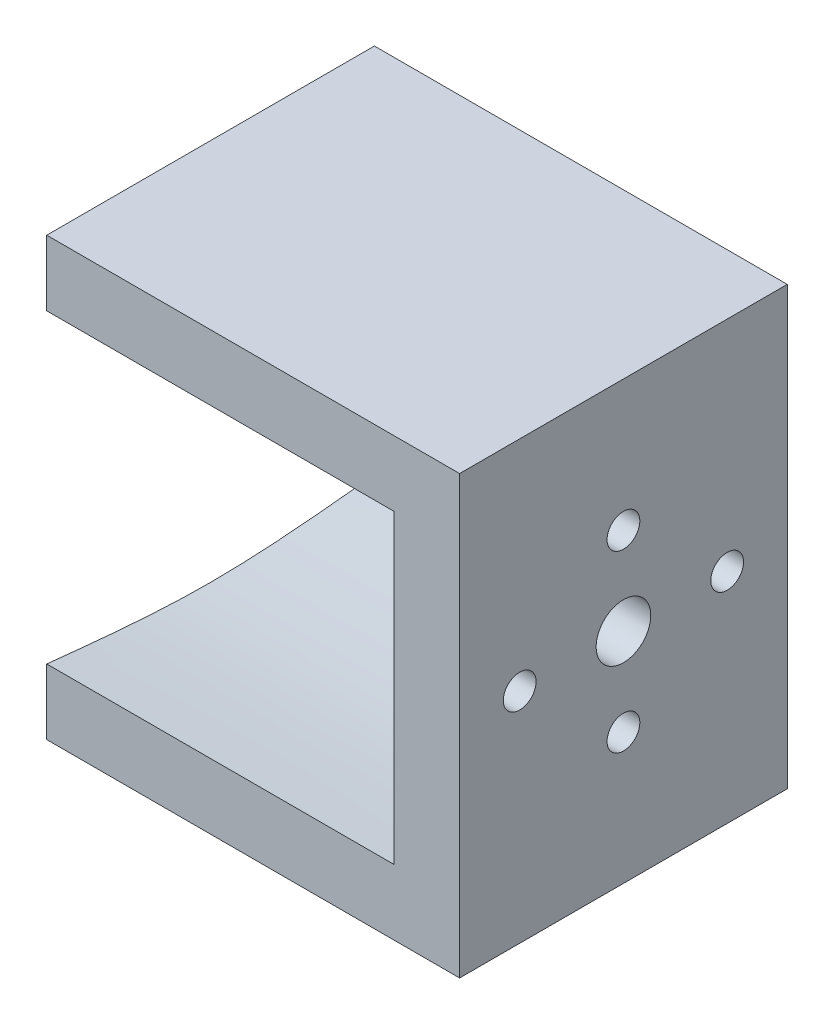
SolidWorks part; units mm, degrees
ref_plane "Front Plane" through (0, 0, 0) normal (0, 0, 1) x (1, 0, 0)
ref_plane "Top Plane" through (0, 0, 0) normal (0, 1, 0) x (1, 0, 0)
ref_plane "Right Plane" through (0, 0, 0) normal (1, 0, 0) x (0, 0, -1)
sketch "Sketch2" plane through (0, 0, 0) normal (0, 0, 1) x (1, 0, 0)
  line L0 (-18.9011, 20) -> (-18.9011, 14)
  line L1 (-18.9011, -20) -> (18.9011, -20)
  line L3 (-18.9011, 20) -> (18.9011, 20)
  line L4 (18.9011, -20) -> (18.9011, 20)
  line L5 (-18.9011, -20) -> (18.9011, 20) construction
  line L6 (-18.9011, 20) -> (18.9011, -20) construction
  line L7 (-18.9011, -14) -> (12.9011, -14)
  line L8 (-18.9011, -14) -> (-18.9011, 14) construction
  line L9 (-18.9011, 14) -> (12.9011, 14)
  line L10 (12.9011, -14) -> (12.9011, 14)
  line L11 (-18.9011, -14) -> (-18.9011, -20)
  line L12 (12.9011, 0) -> (18.9011, 0) construction
  line L13 (12.9011, 14) -> (18.9011, 14) construction
  point P0 (0, 0)
  dimension "D1" = 40
  dimension "D2" = 6
  dimension "D3" = 37.8021
extrude "Boss-Extrude1" add sketch "Sketch2" along normal blind 30 contours L13 L10 L7 L11 L1 L4 region at (0, 19.4496, 0)
sketch "Sketch4" plane through (12.9011, 0, 0) normal (-1, 0, 0) x (0, 0, 1)
  line L0 (30, 0) -> (0, 0) construction
  line L6 (15, 8) -> (15, -8) construction
  line L7 (24.5, 0) -> (5.5, 0) construction
  circle A0 centre (15, 8) radius 1.5
  circle A1 centre (15, 0) radius 2.5
  circle A2 centre (15, -8) radius 1.5
  circle A3 centre (5.5, 0) radius 1.5
  circle A4 centre (24.5, 0) radius 1.5
  point P14 (0, 0)
  point P15 (15, 0)
  point P17 (15, 0)
  point P30 (15, 0)
  dimension "D2" = 3
  dimension "D4" = 5
  dimension "D1" = 8
  dimension "D3" = 9.5
extrude "Cut-Extrude1" cut sketch "Sketch4" against normal through all
sketch "Sketch7" plane through (-18.9011, 0, 0) normal (-1, 0, 0) x (0, 0, 1)
  line L0 (0, -14) -> (30, -14)
  line L1 (16.5, 0) -> (-16.5, 0) construction
  line L2 (0, 14) -> (30, 14)
  spline S0 degree 3 poles (0, -14) (5, -14.5166) (15, -15.5498) (25, -14.5166) (30, -14) knots 0 0 0 0 0.5 1 1 1 1
  spline S1 degree 3 poles (0, 14) (5, 14.5166) (15, 15.5498) (25, 14.5166) (30, 14) knots 0 0 0 0 0.5 1 1 1 1
extrude "Cut-Extrude3" cut sketch "Sketch7" along direction (1, 0, 0) on the side against the normal up to surface (31.8021 mm away) up to face at (12.9011, 8, 16.5)
equation "\"inner radius\"= 230"
equation "\"wall thickness\"= 6 "
equation "\"outer radius\"= \"inner radius\" + 2 * \"wall thickness\""
equation "\"height\" = 40"
equation "\"wheel distance\" = 100"
equation "\"screw length\" = 15"
equation "\"top bottom thickness\" = 4"
equation "\"accel distance\" = 75"
equation "\"tolerance\" = 0.1"
equation "\"D1@Sketch2\"=\"height\""
equation "\"D2@Sketch2\"=\"wall thickness\""
equation "\"D1@Boss-Extrude1\"=\"wheel hole width\""
equation "\"wheel hole width\" = 30"
